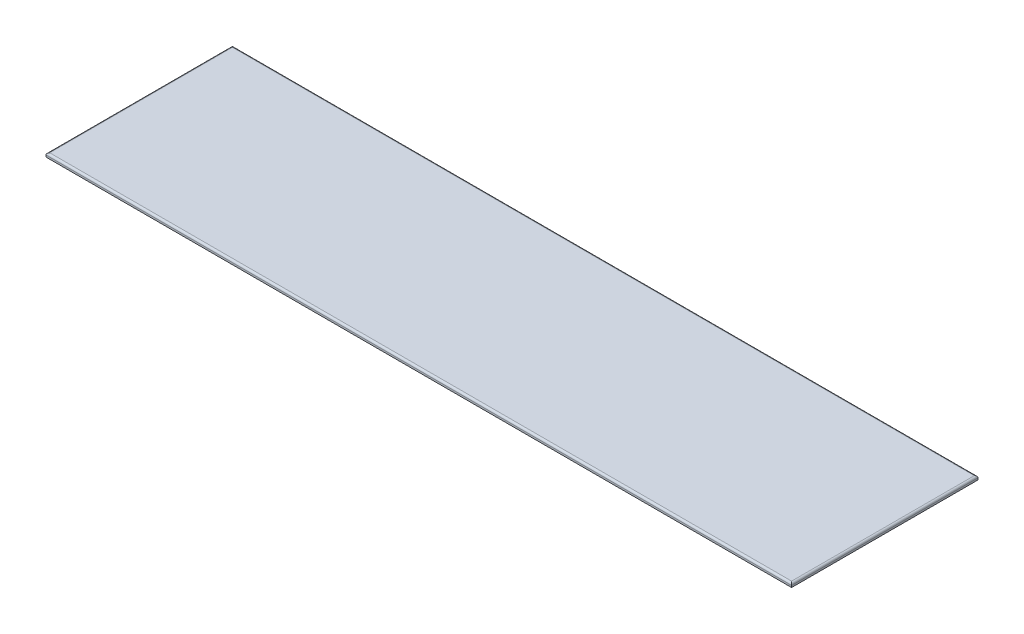
SolidWorks part; units mm, degrees
material "天然橡胶"
ref_plane "前视基准面" through (0, 0, 0) normal (0, 0, 1) x (1, 0, 0)
ref_plane "上视基准面" through (0, 0, 0) normal (0, 1, 0) x (1, 0, 0)
ref_plane "右视基准面" through (0, 0, 0) normal (1, 0, 0) x (0, 0, -1)
sketch "草图1" plane through (0, 0, 0) normal (0, 1, 0) x (1, 0, 0)
  line L1 (0, 0) -> (200, 0)
  line L2 (0, 0) -> (0, 50)
  line L3 (0, 50) -> (200, 50)
  line L4 (200, 0) -> (200, 50)
  dimension "D1" = 50
  dimension "D2" = 200
base flange "基体-法兰1" sketch "草图1" thickness 1 reverse thickness direction no parameters "D1"=0.7366
fillet "圆角1" radius 0.5 4 edges at (200, 0, -25) (100, 0, -50) (0, 0, -25) (100, 0, 0)
sketch "折弯-线1" [suppressed] plane through (0, 0, 0) normal (0, 1, 0) x (1, 0, 0)
sketch "边界框1" [suppressed] plane through (0, 0, 0) normal (0, 1, 0) x (1, 0, 0)
sheet metal parameters "钣金12" thickness 1 parameters "D1"=0.7366
flat pattern "平展型式12" [suppressed]
sketch "折弯-线2" plane through (0, 0, 0) normal (0, 1, 0) x (1, 0, 0)
sketch3d "边界框2" [suppressed]
  line L0 (200, 50, -1) -> (0, 50, -1) construction
  line L1 (200, 0, -1) -> (0, 0, -1) construction
  line L2 (200, 50, -1) -> (200, 0, -1) construction
  line L3 (0, 50, -1) -> (0, 0, -1) construction
